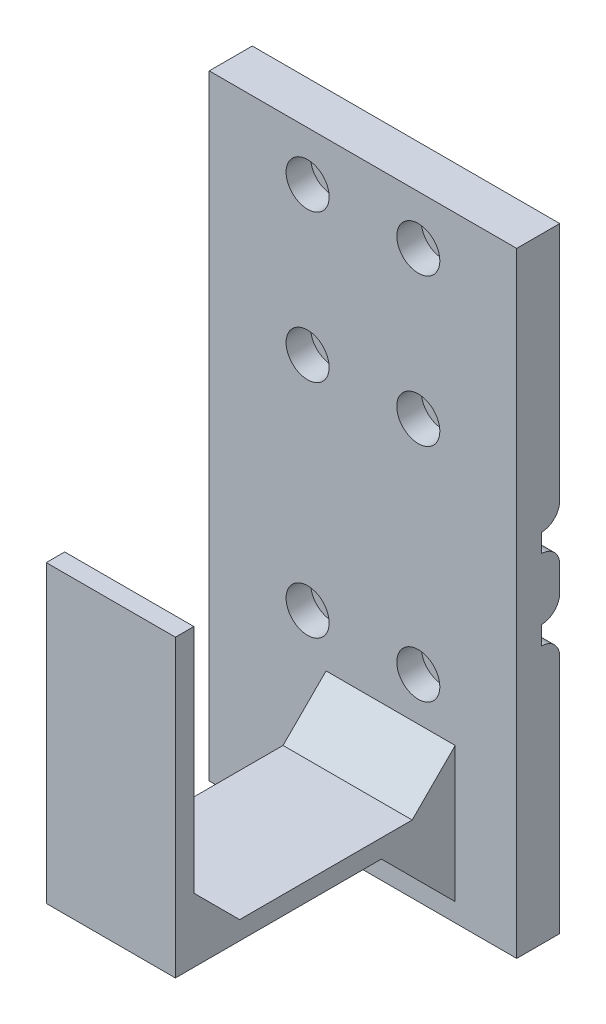
SolidWorks part; units mm, degrees
ref_plane "Front Plane" through (0, 0, 0) normal (0, 0, 1) x (1, 0, 0)
ref_plane "Top Plane" through (0, 0, 0) normal (0, 1, 0) x (1, 0, 0)
ref_plane "Right Plane" through (0, 0, 0) normal (1, 0, 0) x (0, 0, -1)
sketch "Sketch1" plane through (0, 0, 0) normal (0, 0, 1) x (1, 0, 0)
  line L1 (-25, -50) -> (25, -50)
  line L2 (-25, -50) -> (-25, 50)
  line L3 (-25, 50) -> (25, 50)
  line L4 (25, -50) -> (25, 50)
  line L5 (-25, -50) -> (25, 50) construction
  line L6 (-25, 50) -> (25, -50) construction
  point P0 (0, 0)
  dimension "D1" = 50
  dimension "D2" = 100
sketch "Sketch2" plane through (0, 0, 0) normal (0, 0, 1) x (1, 0, 0)
  line L0 (-9, 42) -> (9, 42) construction
  line L1 (9, 42) -> (9, 18) construction
  line L2 (9, 18) -> (-9, 18) construction
  line L3 (-9, 18) -> (-9, 42) construction
  line L4 (-9, 42) -> (9, 18) construction
  line L5 (9, 42) -> (-9, 18) construction
  line L6 (-9, -18) -> (9, -18) construction
  line L7 (9, -18) -> (9, -42) construction
  line L8 (9, -42) -> (-9, -42) construction
  line L9 (-9, -42) -> (-9, -18) construction
  line L10 (-9, -18) -> (9, -42) construction
  line L11 (9, -18) -> (-9, -42) construction
  line L12 (-9, 18) -> (-9, -18) construction
  line L13 (-9, -18) -> (9, 18) construction
  line L14 (9, 18) -> (9, -18) construction
  line L15 (9, -18) -> (-9, 18) construction
  circle A0 centre (-9, 42) radius 1.6
  circle A1 centre (9, 42) radius 1.6
  circle A2 centre (-9, 18) radius 1.6
  circle A3 centre (9, 18) radius 1.6
  circle A4 centre (9, -18) radius 1.6
  circle A5 centre (-9, -18) radius 1.6
  circle A6 centre (-9, -42) radius 1.6
  circle A7 centre (9, -42) radius 1.6
  point P2 (0, 0)
  point P5 (0, 0)
  dimension "D1" = 3.2
  dimension "D2" = 24
  dimension "D3" = 36
  dimension "D4" = 24
  dimension "D5" = 18
extrude "Boss-Extrude1" add sketch "Sketch1" against normal blind 7
extrude "Cut-Extrude1" cut sketch "Sketch2" against normal up to next
sketch "Sketch4" plane through (0, 0, 0) normal (0, 0, 1) x (1, 0, 0)
  line L0 (-25, -32) -> (25, -32) construction
  line L1 (-25, 50) -> (-25, -50) construction
  line L2 (25, -50) -> (25, 50) construction
  line L3 (-25, -35) -> (25, -35) construction
  line L4 (15, -32) -> (15, -35)
  line L5 (-6, -32) -> (-6, -35)
  line L6 (-6, -32) -> (15, -32)
  line L7 (15, -35) -> (-6, -35)
  dimension "D1" = 18
  dimension "D2" = 3
  dimension "D3" = 10
  dimension "D4" = 21
extrude "Boss-Extrude2" add sketch "Sketch4" along normal blind 45.5
sketch "Sketch5" plane through (0, -32, 0) normal (0, 1, 0) x (1, 0, 0)
  line L0 (15, -45.5) -> (15, 0) construction
  line L1 (-6, -45.5) -> (15, -45.5)
  line L2 (-6, -45.5) -> (-6, -35.1) construction
  line L3 (-6, -35.1) -> (15, -35.1) construction
  line L4 (15, -45.5) -> (15, -35.1) construction
  line L5 (-6, -42.5) -> (15, -42.5)
  line L6 (15, -42.5) -> (15, -45.5)
  line L7 (-6, -45.5) -> (-6, -42.5)
  dimension "D1" = 10.4
  dimension "D2" = 3
extrude "Boss-Extrude3" add sketch "Sketch5" along normal blind 45
ref_plane "Plane1" through (-6, 0, 0) normal (-1, 0, 0) x (0, 0, 1)
sketch "Sketch6" plane through (-6, 0, 0) normal (-1, 0, 0) x (0, 0, 1)
  line L0 (42.5, -24.55) -> (35.05, -32)
  line L1 (42.5, -32) -> (35.05, -32)
  line L2 (42.5, -32) -> (42.5, -24.55)
  line L3 (42.5, -24.55) -> (35.05, -24.55) construction
  line L4 (35.05, -32) -> (35.05, -24.55) construction
  dimension "D1" = 7.45
extrude "Boss-Extrude4" add sketch "Sketch6" against normal up to surface (21 mm away) up to face at (15, -18, 29.3333)
sketch "Sketch7" plane through (0, 0, 0) normal (0, 0, 1) x (1, 0, 0)
  line L0 (-6, -35) -> (15, -35) construction
  line L1 (15, -35) -> (-6, -35)
  line L2 (15, -35) -> (15, -47)
  line L3 (15, -47) -> (-6, -47)
  line L4 (-6, -35) -> (-6, -47)
  dimension "D1" = 12
sketch "Sketch8" plane through (0, -35, 0) normal (0, -1, 0) x (1, 0, 0)
  line L0 (15, 45.5) -> (15, 0) construction
  line L1 (-6, 0) -> (15, 0)
  line L2 (-6, 0) -> (-6, 12)
  line L3 (-6, 12) -> (15, 12)
  line L4 (15, 0) -> (15, 12)
  dimension "D1" = 12
loft "Loft1" add profiles "Sketch8", "Sketch7" connector at (-6, -35, 12) connector at (-6, -47, 0)
sketch "Sketch3" plane through (0, 0, 0) normal (0, 0, 1) x (1, 0, 0)
  line L0 (-9, 42) -> (9, 18) construction
  line L1 (9, 18) -> (9, 42) construction
  line L2 (9, 42) -> (-9, 18) construction
  line L3 (-9, 18) -> (-9, 42) construction
  line L4 (-9, 42) -> (9, 42) construction
  line L5 (-9, 18) -> (9, 18) construction
  line L6 (9, 18) -> (-9, -18) construction
  line L7 (-9, -18) -> (9, -18) construction
  line L8 (9, -18) -> (-9, 18) construction
  line L9 (-9, 18) -> (-9, -18) construction
  line L10 (-9, -18) -> (-9, -42) construction
  line L11 (-9, -42) -> (9, -42) construction
  line L12 (9, -42) -> (-9, -18) construction
  line L13 (9, 18) -> (9, -18) construction
  line L14 (9, -18) -> (9, -42) construction
  line L15 (9, -18) -> (-9, -42) construction
  circle A0 centre (-9, 42) radius 3.5
  circle A1 centre (9, 42) radius 3.5
  circle A2 centre (-9, 18) radius 3.5
  circle A3 centre (9, 18) radius 3.5
  circle A4 centre (-9, -18) radius 3.5
  circle A5 centre (9, -18) radius 3.5
  circle A6 centre (9, -42) radius 3.5
  circle A7 centre (-9, -42) radius 3.5
  point P24 (0, 0)
  point P25 (0, 0)
  dimension "D1" = 7
  dimension "D2" = 18
  dimension "D3" = 24
  dimension "D4" = 36
  dimension "D5" = 24
extrude "Cut-Extrude2" cut sketch "Sketch3" against normal blind 24 from offset 20
sketch "Sketch10" plane through (-6, 0, 0) normal (-1, 0, 0) x (0, 0, 1)
  line L0 (35.05, -32) -> (0, -32) construction
  line L1 (7, -32) -> (0, -32)
  line L2 (0, -32) -> (0, -25)
  line L3 (0, 50) -> (0, -50) construction
  line L4 (0, -25) -> (7, -32)
  dimension "D1" = 7
extrude "Boss-Extrude5" add sketch "Sketch10" against normal up to surface (21 mm away) up to face at (15, -22.6313, 30.725)
sketch "Sketch11" plane through (0, 0, -7) normal (0, 0, -1) x (-1, 0, 0)
  line L0 (-25, 50) -> (25, -50) construction
  line L1 (25, -50) -> (25, 50) construction
  line L2 (25, 50) -> (-25, -50) construction
  line L3 (-25, 0) -> (25, 0) construction
  line L4 (-25, -50) -> (-25, 50) construction
  line L5 (-25, 8) -> (25, 8)
  line L6 (-25, -8) -> (25, -8)
  line L7 (-25, 5) -> (25, 5)
  line L8 (-25, -5) -> (25, -5)
  arc A0 (-25, 8) -> (-25, -8) centre (-25, 0) ccw
  arc A1 (25, -8) -> (25, 8) centre (25, 0) ccw
  arc A2 (25, -5) -> (25, 5) centre (25, 0) ccw
  arc A3 (-25, 5) -> (-25, -5) centre (-25, 0) ccw
  point P12 (0, 0)
  dimension "D1" = 16
  dimension "D2" = 3
extrude "Cut-Extrude3" cut sketch "Sketch11" against normal blind 3
fillet "Fillet1" radius 3 4 edges at (0, -8, -7) (0, 8, -7) (0, -5, -7) (0, 5, -7)
